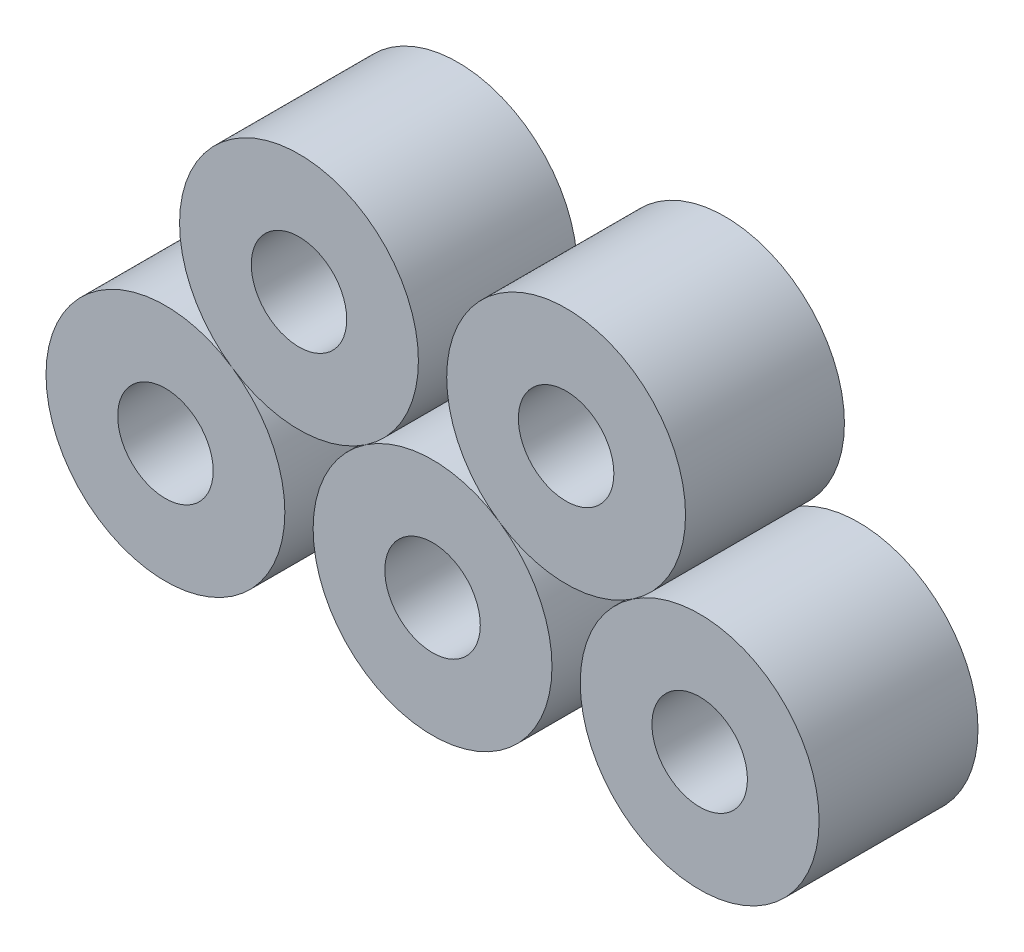
SolidWorks part; units mm, degrees
ref_plane "Płaszczyzna przednia" through (0, 0, 0) normal (0, 0, 1) x (1, 0, 0)
ref_plane "Płaszczyzna górna" through (0, 0, 0) normal (0, 1, 0) x (1, 0, 0)
ref_plane "Płaszczyzna prawa" through (0, 0, 0) normal (1, 0, 0) x (0, 0, -1)
sketch "Szkic1" plane through (0, 0, 0) normal (0, 0, 1) x (1, 0, 0)
  circle A0 centre (0, 0) radius 381
  circle A1 centre (0, 0) radius 953
  circle A2 centre (2131.6433, 0) radius 381
  circle A3 centre (2131.6433, 0) radius 953
  circle A4 centre (4263.2867, 0) radius 381
  circle A5 centre (4263.2867, 0) radius 953
  circle A6 centre (3197.465, 1580.1456) radius 381
  circle A7 centre (3197.465, 1580.1456) radius 953
  circle A10 centre (1065.8217, 1580.1456) radius 381
  circle A11 centre (1065.8217, 1580.1456) radius 953
  circle A12 centre (5329.1084, 1580.1456) radius 953 [skipped]
  circle A13 centre (5329.1084, 1580.1456) radius 381 [skipped]
  dimension "D1" = 762
  dimension "D2" = 1906
  dimension "D3" = 3
  dimension "D4" = 2
extrude "Dodanie-wyciągnięcie2" add sketch "Szkic1" along normal blind 1268 contours A0 | A1 | A10 | A11 | A6 | A7 | A2 | A3 | A4 | A5
ref_axis "Oś1" through (0, 0, 1268) along (0, 0, -1)
ref_axis "Oś2" through (2131.6433, 0, 1268) along (0, 0, -1)
ref_axis "Oś3" through (4263.2867, 0, 1268) along (0, 0, -1)
ref_axis "Oś4" through (1065.8217, 1580.1456, 1268) along (0, 0, -1)
ref_axis "Oś5" through (3197.465, 1580.1456, 1268) along (0, 0, -1)
